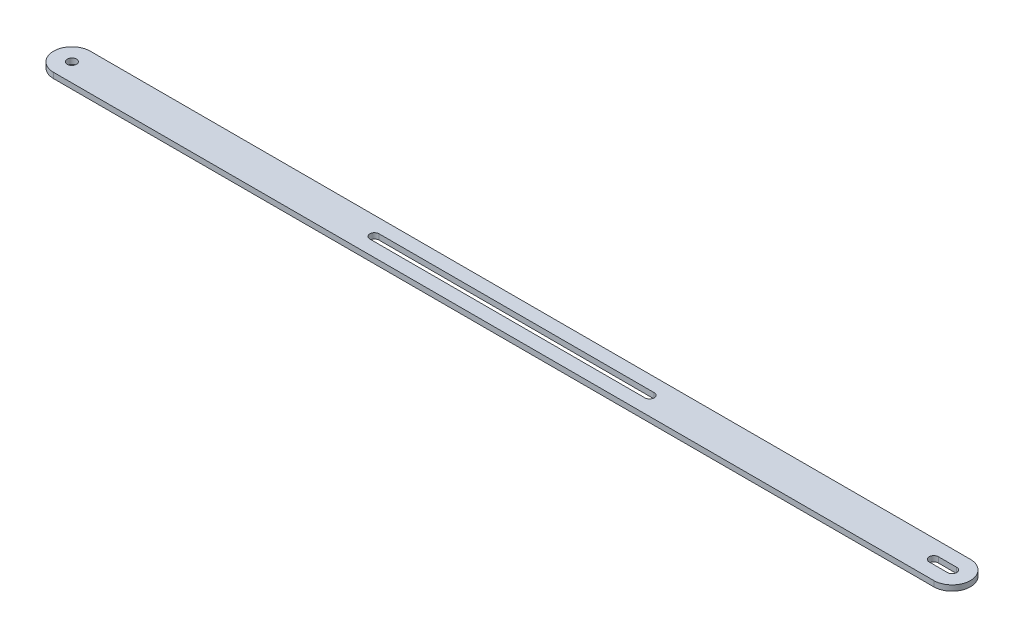
SolidWorks part; units mm, degrees
ref_plane "Front Plane" through (0, 0, 0) normal (0, 0, 1) x (1, 0, 0)
ref_plane "Top Plane" through (0, 0, 0) normal (0, 1, 0) x (1, 0, 0)
ref_plane "Right Plane" through (0, 0, 0) normal (1, 0, 0) x (0, 0, -1)
sketch "Sketch1" plane through (0, 0, 0) normal (0, 1, 0) x (1, 0, 0)
  line L0 (-240, 0) -> (240, 0) construction
  line L1 (-240, 10) -> (240, 10)
  line L2 (-240, -10) -> (240, -10)
  line L3 (240, 0) -> (230, 0) construction
  line L4 (240, -2.5) -> (230, -2.5)
  line L5 (240, 2.5) -> (230, 2.5)
  arc A0 (-240, 10) -> (-240, -10) centre (-240, 0) ccw
  arc A1 (240, -10) -> (240, 10) centre (240, 0) ccw
  circle A3 centre (-240, 0) radius 2.5
  arc A4 (240, -2.5) -> (240, 2.5) centre (240, 0) ccw
  arc A5 (230, 2.5) -> (230, -2.5) centre (230, 0) ccw
  point P2 (0, 0)
  point P12 (235, 0)
  dimension "D1" = 10
  dimension "D2" = 5
  dimension "D4" = 2.5
  dimension "D3" = 480
  dimension "D5" = 10
extrude "Boss-Extrude1" add sketch "Sketch1" along normal blind 3
sketch "Sketch2" plane through (0, 3, 0) normal (0, 1, 0) x (1, 0, 0)
  line L0 (-75, 0) -> (75, 0) construction
  line L1 (-75, 2.5) -> (75, 2.5)
  line L2 (-75, -2.5) -> (75, -2.5)
  arc A0 (-75, 2.5) -> (-75, -2.5) centre (-75, 0) ccw
  arc A1 (75, -2.5) -> (75, 2.5) centre (75, 0) ccw
  point P2 (0, 0)
  dimension "D1" = 2.5
  dimension "D2" = 150
extrude "Cut-Extrude1" cut sketch "Sketch2" against normal through all
